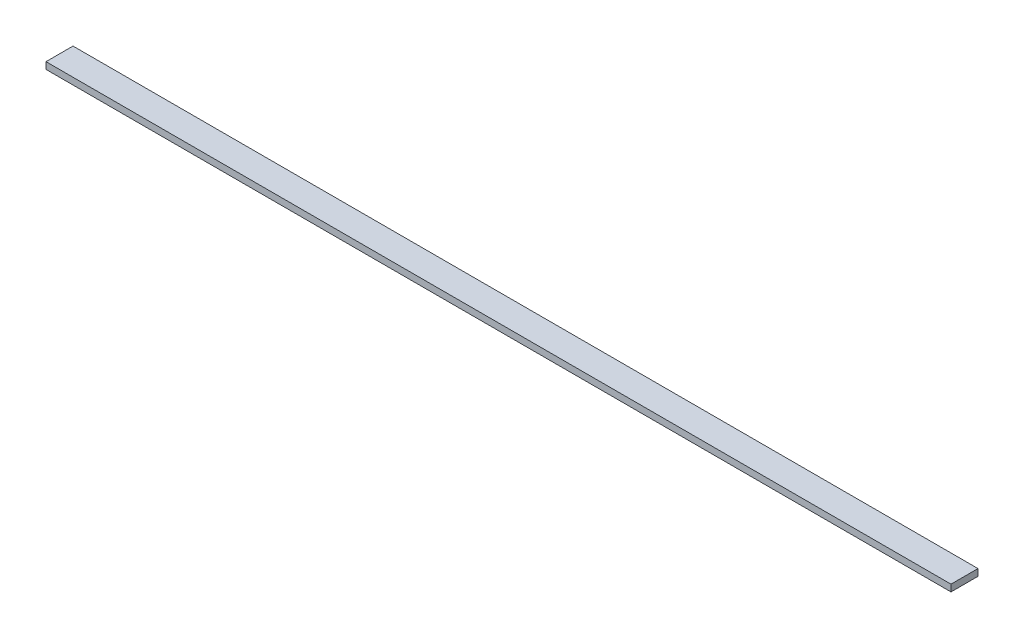
SolidWorks part; units mm, degrees
ref_plane "Front Plane" through (0, 0, 0) normal (0, 0, 1) x (1, 0, 0)
ref_plane "Top Plane" through (0, 0, 0) normal (0, 1, 0) x (1, 0, 0)
ref_plane "Right Plane" through (0, 0, 0) normal (1, 0, 0) x (0, 0, -1)
sketch "Sketch1" plane through (0, 0, 0) normal (0, 1, 0) x (1, 0, 0)
  line L1 (-425.45, -12.7) -> (425.45, -12.7)
  line L2 (-425.45, -12.7) -> (-425.45, 12.7)
  line L3 (-425.45, 12.7) -> (425.45, 12.7)
  line L4 (425.45, -12.7) -> (425.45, 12.7)
  line L5 (-425.45, -12.7) -> (425.45, 12.7) construction
  line L6 (-425.45, 12.7) -> (425.45, -12.7) construction
  point P0 (0, 0)
  dimension "D1" = 850.9
  dimension "D2" = 25.4
extrude "Boss-Extrude1" add sketch "Sketch1" along normal blind 6.35
equation "\"horizontal-component-length\"= \"railing-width\" - \"railing padding\""
equation "\"horizontal-component-width\"= 1in"
equation "\"D1@Sketch1\"=\"horizontal-component-length\""
equation "\"D2@Sketch1\"=\"horizontal-component-width\""
equation "\"material-thickness\"= .25in"
equation "\"D1@Boss-Extrude1\"=\"material-thickness\""
equation "\"railing-width\"= 34in"
equation "\"railing padding\"= .5in"
